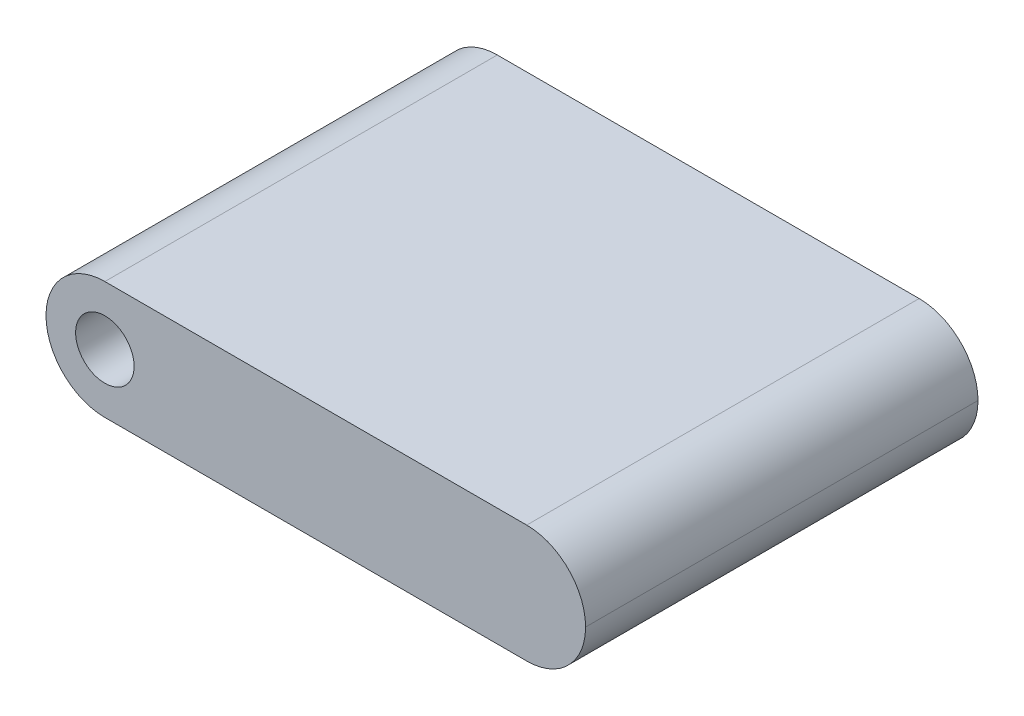
SolidWorks part; units mm, degrees
ref_plane "Front Plane" through (0, 0, 0) normal (0, 0, 1) x (1, 0, 0)
ref_plane "Top Plane" through (0, 0, 0) normal (0, 1, 0) x (1, 0, 0)
ref_plane "Right Plane" through (0, 0, 0) normal (1, 0, 0) x (0, 0, -1)
sketch "Sketch1" plane through (0, 0, 0) normal (0, 0, 1) x (1, 0, 0)
  line L4 (49, 6) -> (-6, 6)
  line L5 (-6, 6) -> (-6, -6)
  line L6 (0, 0) -> (-6, 0) construction
  line L7 (-6, -6) -> (49, -6)
  line L8 (49, -6) -> (49, 6)
  circle A0 centre (0, 0) radius 2.98
  dimension "D1" = 5.96
  dimension "D2" = 12
  dimension "D3" = 49
  dimension "D6" = 6
extrude "Boss-Extrude1" add sketch "Sketch1" along normal mid plane 40
fillet "Fillet2" radius 6 4 edges at (49, -6, 0) (49, 6, 0) (-6, -6, 0) (-6, 6, 0)
